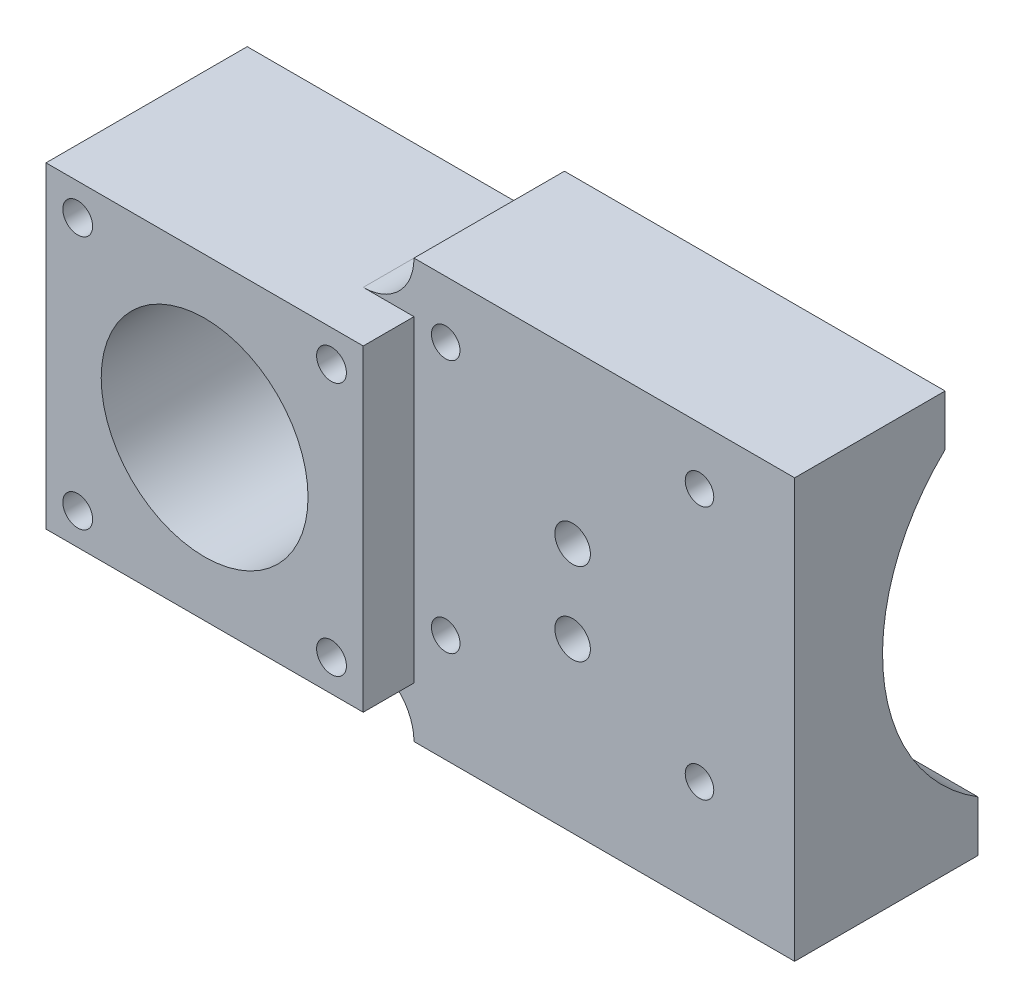
SolidWorks part; units mm, degrees
ref_plane "Front Plane" through (0, 0, 0) normal (0, 0, 1) x (1, 0, 0)
ref_plane "Top Plane" through (0, 0, 0) normal (0, 1, 0) x (1, 0, 0)
ref_plane "Right Plane" through (0, 0, 0) normal (1, 0, 0) x (0, 0, -1)
sketch "Sketch1" plane through (0, 0, 0) normal (0, 0, 1) x (1, 0, 0)
  line L1 (-25, 23) -> (25, 23)
  line L2 (-25, 23) -> (-25, -27)
  line L3 (-25, -27) -> (25, -27)
  line L4 (25, 23) -> (25, -27)
  line L5 (-25, 23) -> (25, -27) construction
  line L6 (-25, -27) -> (25, 23) construction
  circle A0 centre (0, -2) radius 16.3
  circle A1 centre (-20, 18) radius 2.35
  circle A2 centre (20, 18) radius 2.35
  circle A3 centre (20, -22) radius 2.35
  circle A4 centre (-20, -22) radius 2.35
  point P0 (0, -2)
  dimension "D4" = 32.6
  dimension "D6" = 4.7
  dimension "D1" = 2
  dimension "D2" = 50
  dimension "D3" = 50
  dimension "D5" = 20
  dimension "D7" = 20
  dimension "D9" = 20
  dimension "D10" = 20
extrude "Boss-Extrude1" add sketch "Sketch1" along normal blind 53.6
sketch "Sketch2" plane through (0, 0, 0) normal (1, 0, 0) x (0, 0, -1)
  circle A0 centre (0, 0) radius 31.75
  dimension "D1" = 63.5
extrude "Cut-Extrude1" cut sketch "Sketch2" against normal through all and the other way through all
sketch "Sketch3" plane through (-25, 0, 0) normal (-1, 0, 0) x (0, 0, 1)
  line L3 (53.6, 23) -> (21.8875, 23)
  line L4 (16.7052, -27) -> (53.6, -27)
  line L5 (53.6, -27) -> (53.6, 23)
  line L6 (53.6, 23) -> (21.8875, 23)
  line L7 (16.7052, -27) -> (53.6, -27)
  line L8 (53.6, -27) -> (53.6, 23)
  arc A1 (16.7052, -27) -> (21.8875, 23) centre (0, 0) ccw
  arc A2 (16.7052, -27) -> (21.8875, 23) centre (0, 0) ccw
  dimension "D1" = 0
sketch "Sketch4" plane through (25, 0, 0) normal (1, 0, 0) x (0, 0, -1)
  line L0 (-53.6, -27) -> (-53.6, -35)
  line L1 (-53.6, -35) -> (-16.7052, -35)
  line L2 (-16.7052, -35) -> (-16.7052, -27)
  line L3 (-53.6, -27) -> (-16.7052, -27)
  line L4 (-21.8875, 23) -> (-53.6, 23)
  line L5 (-53.6, 23) -> (-53.6, -27)
  line L8 (-53.6, 23) -> (-53.6, -27)
  line L9 (-21.8875, 23) -> (-21.8875, 31)
  line L10 (-21.8875, 31) -> (-53.6, 31)
  line L11 (-53.6, 31) -> (-53.6, 23)
  arc A1 (-21.8875, 23) -> (-16.7052, -27) centre (0, 0) ccw
  arc A2 (-21.8875, 23) -> (-16.7052, -27) centre (0, 0) ccw
  dimension "D2" = 8
  dimension "D1" = 0
extrude "Boss-Extrude3" add sketch "Sketch4" along normal blind 60
sketch "Sketch12" plane through (0, 0, 53.6) normal (0, 0, 1) x (1, 0, 0)
  line L0 (25, 31) -> (25, -35)
  line L1 (25, -35) -> (85, -35)
  line L2 (85, -35) -> (85, 31)
  line L3 (85, 31) -> (85, -35) construction
  line L4 (85, 31) -> (25, 31) construction
  line L5 (85, 31) -> (25, 31)
extrude "Cut-Extrude7" cut sketch "Sketch12" against normal blind 8
sketch "Sketch9" plane through (0, 0, 0) normal (0, 0, 1) x (1, 0, 0)
  line L0 (30, 22) -> (30, -18) construction
  line L1 (30, -18) -> (70, -18) construction
  line L2 (70, -18) -> (70, 22) construction
  line L3 (70, 22) -> (30, 22) construction
  line L4 (85, 31) -> (25, 31) construction
  line L6 (85, 2) -> (25, 2) construction
  circle A0 centre (30, 22) radius 2.25
  circle A1 centre (70, 22) radius 2.25
  circle A2 centre (70, -18) radius 2.25
  circle A3 centre (30, -18) radius 2.25
  point P0 (30, 22)
  point P2 (70, 22)
  point P4 (70, -18)
  point P6 (30, -18)
  point P14 (0, 0)
  point P15 (0, 0)
  point P20 (0, 0)
  point P25 (70, 2)
  dimension "D4" = 4.5
  dimension "D1" = 60
  dimension "D2" = 5
  dimension "D3" = 40
  dimension "D5" = 29
extrude "Cut-Extrude5" cut sketch "Sketch9" against normal through all both and the other way through all
sketch "Sketch10" plane through (0, 0, 45.6) normal (0, 0, 1) x (1, 0, 0)
  line L0 (50, 4.5) -> (50, -8.5) construction
  line L1 (85, -2) -> (25, -2) construction
  line L2 (85, 23) -> (85, -27) construction
  line L3 (30, 22) -> (70, 22) construction
  line L4 (70, 22) -> (50, 22) construction
  line L5 (50, 22) -> (50, -27) construction
  line L6 (-25, -27) -> (25, -27) construction
  circle A0 centre (50, 4.5) radius 2.8
  circle A1 centre (50, -8.5) radius 2.8
  point P8 (50, -2)
  dimension "D1" = 5.6
  dimension "D2" = 60
  dimension "D3" = 13
extrude "Cut-Extrude6" cut sketch "Sketch10" against normal blind 10 and the other way through all
fillet "Fillet1" radius 8 2 edges at (25, 23, 33.7437) (25, -27, 31.1526)
